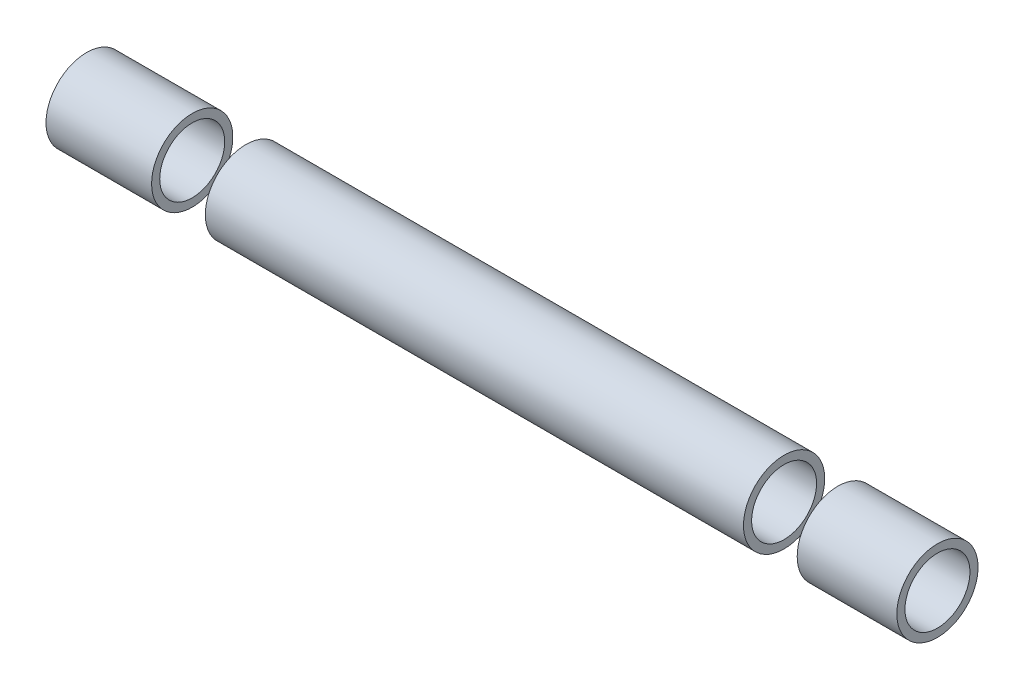
SolidWorks part; units mm, degrees
material "PC High Viscosity"
ref_plane "Front Plane" through (0, 0, 0) normal (0, 0, 1) x (1, 0, 0)
ref_plane "Top Plane" through (0, 0, 0) normal (0, 1, 0) x (1, 0, 0)
ref_plane "Right Plane" through (0, 0, 0) normal (1, 0, 0) x (0, 0, -1)
sketch "Sketch1" plane through (0, 0, 0) normal (1, 0, 0) x (0, 0, -1)
  circle A0 centre (0, 0) radius 15.875
  dimension "D1" = 31.75
extrude "Extrude-Thin1" add sketch "Sketch1" along normal mid plane 334.899 thin thin type one direction reverse wall 3.175
sketch "Sketch2" plane through (0, 0, 0) normal (0, 0, 1) x (1, 0, 0)
  line L0 (-167.4495, -15.875) -> (167.4495, -15.875) construction
  line L1 (105.1745, -15.875) -> (126.1745, -15.875)
  line L2 (105.1745, -15.875) -> (105.1745, 15.875)
  line L3 (105.1745, 15.875) -> (126.1745, 15.875)
  line L4 (126.1745, -15.875) -> (126.1745, 15.875)
  line L5 (167.4495, 15.875) -> (-167.4495, 15.875) construction
  line L6 (167.4495, -15.875) -> (167.4495, 15.875) construction
  line L7 (0, 0) -> (0, 11.1276) construction
  line L8 (-126.1745, -15.875) -> (-126.1745, 15.875)
  line L9 (-105.1745, 15.875) -> (-126.1745, 15.875)
  line L10 (-105.1745, -15.875) -> (-105.1745, 15.875)
  line L11 (-105.1745, -15.875) -> (-126.1745, -15.875)
  line L13 (167.4495, -15.875) -> (165.1254, -15.875)
  line L14 (167.4495, -15.875) -> (167.4495, 15.875)
  line L15 (167.4495, 15.875) -> (165.1254, 15.875)
  line L16 (165.1254, -15.875) -> (165.1254, 15.875)
  dimension "D1" = 41.275
  dimension "D2" = 21
  dimension "D3" = 2.3241
extrude "Cut-Extrude1" cut sketch "Sketch2" against normal through all both and the other way through all
equation "\"D2@Sketch2\"=21mm"
